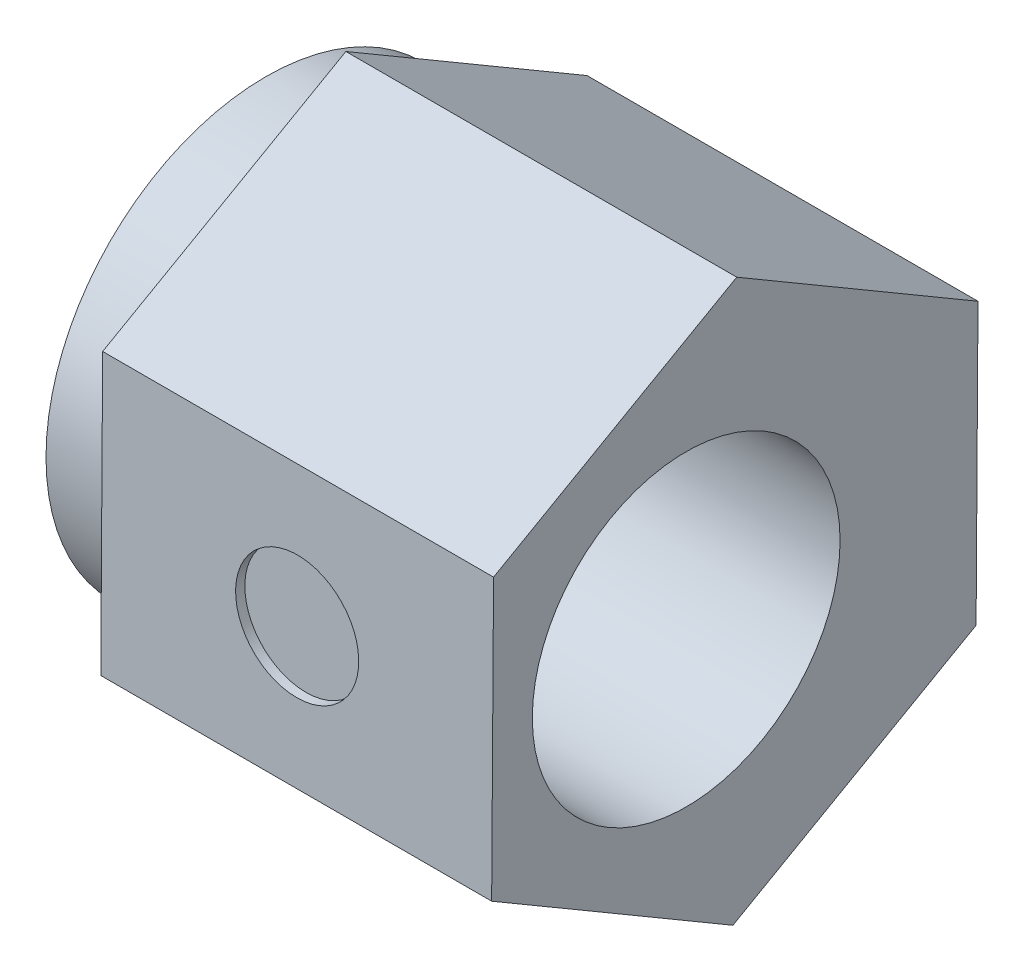
SolidWorks part; units mm, degrees
ref_plane "Front Plane" through (0, 0, 0) normal (0, 0, 1) x (1, 0, 0)
ref_plane "Top Plane" through (0, 0, 0) normal (0, 1, 0) x (1, 0, 0)
ref_plane "Right Plane" through (0, 0, 0) normal (1, 0, 0) x (0, 0, -1)
sketch "Sketch2" plane through (0, 0, 0) normal (1, 0, 0) x (0, 0, -1)
  line L1 (3.9194, -2.2986) -> (3.9504, 2.245)
  line L2 (3.9504, 2.245) -> (0.0309, 4.5436)
  line L3 (0.0309, 4.5436) -> (-3.9194, 2.2986)
  line L4 (-3.9194, 2.2986) -> (-3.9504, -2.245)
  line L5 (-3.9504, -2.245) -> (-0.0309, -4.5436)
  line L6 (-0.0309, -4.5436) -> (3.9194, -2.2986)
  circle A0 centre (0, 0) radius 3.935 construction
  dimension "D1" = 7.87
extrude "Boss-Extrude1" add sketch "Sketch2" along normal blind 6.35
sketch "Sketch4" plane through (0, 0, 0) normal (-1, 0, 0) x (0, 0, 1)
  circle A0 centre (0, 0) radius 3.57
  dimension "D1" = 7.14
extrude "Boss-Extrude2" add sketch "Sketch4" along normal blind 1.27
sketch "Sketch3" plane through (-1.27, 0, 0) normal (-1, 0, 0) x (0, 0, 1)
  line L0 (0, 0) -> (0.79, 0) construction
  circle A0 centre (0.79, 0) radius 2.5
  dimension "D1" = 5
  dimension "D2" = 0.79
extrude "Cut-Extrude1" cut sketch "Sketch3" against normal through all
sketch "Sketch5" plane through (0, 0.0268, 3.9349) normal (0, -0.0068, -1) x (1, 0, 0)
  line L0 (0, -2.2719) -> (0, 2.2719) construction
  line L6 (0, 0) -> (6.35, 0) construction
  line L8 (6.35, -2.2719) -> (6.35, 2.2719) construction
  circle A0 centre (3.175, 0) radius 1
  point P5 (0, 0)
  point P8 (6.35, 0)
  point P10 (3.175, 0)
  dimension "D1" = 2
extrude "Cut-Extrude3" cut sketch "Sketch5" along normal blind 0.15
